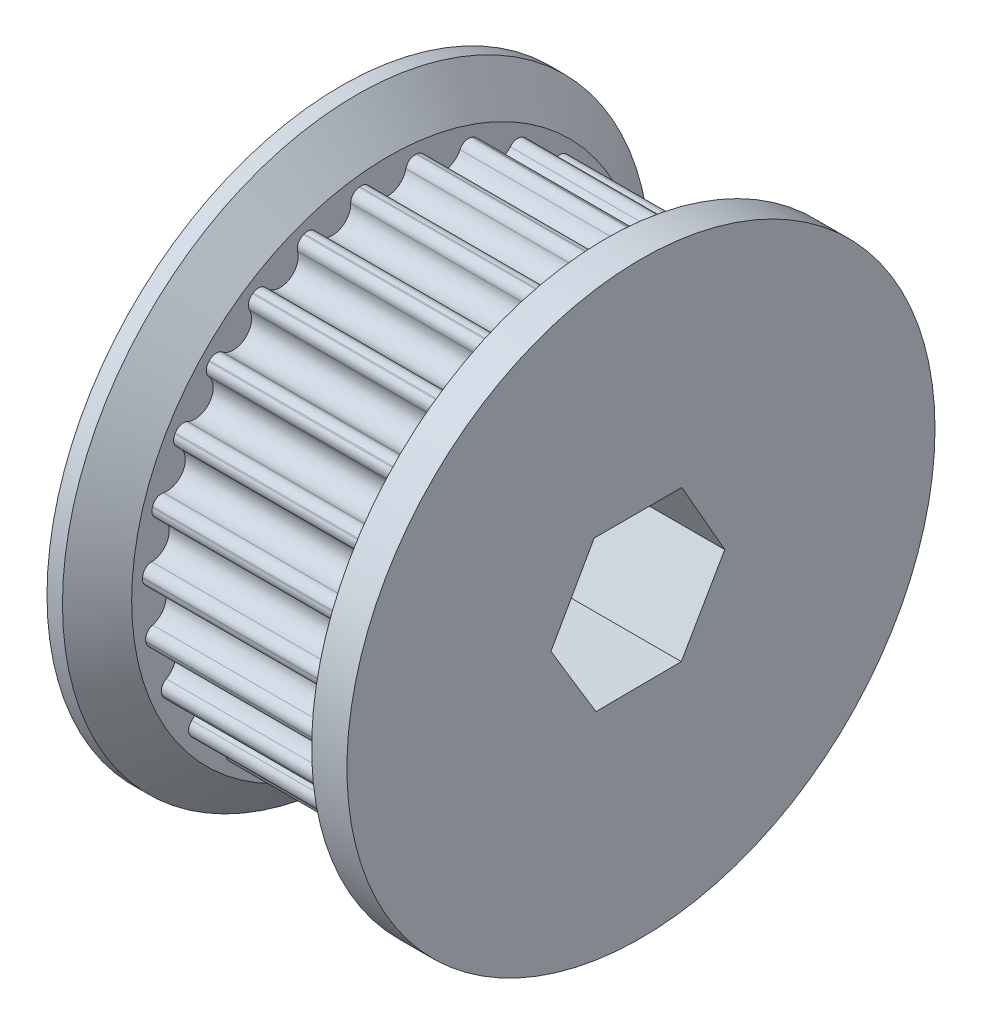
SolidWorks part; units mm, degrees
ref_plane "Front Plane" through (0, 0, 0) normal (0, 0, 1) x (1, 0, 0)
ref_plane "Top Plane" through (0, 0, 0) normal (0, 1, 0) x (1, 0, 0)
ref_plane "Right Plane" through (0, 0, 0) normal (1, 0, 0) x (0, 0, -1)
sketch "Sketch1" plane through (0, 0, 0) normal (1, 0, 0) x (0, 0, -1)
  circle A0 centre (0, 0) radius 20.915
  dimension "D1" = 41.83
extrude "Boss-Extrude1" add sketch "Sketch1" along normal blind 18.5 contours A0
sketch "Sketch8" plane through (18.5, 0, 0) normal (1, 0, 0) x (0, 0, -1)
  line L1 (0, 0) -> (0, 50.3807) construction
  line L7 (-2.5, 21.3391) -> (0, 0) construction
  line L8 (0, 0) -> (2.5, 21.3391) construction
  circle A0 centre (0, 0) radius 21.485 construction
  circle A2 centre (0, 0) radius 20.915 construction
  arc A3 (-1.4883, 20.862) -> (1.4883, 20.862) centre (0, 20.4573) ccw
  arc A6 (-1.4883, 20.862) -> (1.4883, 20.862) centre (0, 0) cw
  point P15 (0, 18.915)
  point P16 (0, 20.915)
  dimension "D4" = 1.5423
  dimension "D2" = 42.97
  dimension "D1" = 5
  dimension "D3" = 2.5
  dimension "D5" = 2
sketch "Sketch9" plane through (0, 0, 0) normal (-1, 0, 0) x (0, 0, 1)
  line L0 (-3.4711, 6.4445) -> (-7.1255, 0.0437)
  line L1 (-7.1255, 0.0437) -> (-3.4298, -6.3571)
  line L2 (-3.4298, -6.3571) -> (3.8268, -6.4097)
  line L3 (3.8268, -6.4097) -> (7.6559, -0.0635)
  line L4 (7.6559, -0.0635) -> (3.9818, 6.4445)
  line L5 (3.9818, 6.4445) -> (-3.4711, 6.4445)
extrude "Cut-Extrude6" cut sketch "Sketch8" against normal blind 43 contours A6 A3
fillet "Fillet4" radius 0.8 2 edges at (9.25, 20.862, -1.4883) (9.25, 20.862, 1.4883)
sketch "Sketch10" plane through (18.5, 0, 0) normal (1, 0, 0) x (0, 0, -1)
  circle A0 centre (0, 0) radius 25
  dimension "D1" = 50
sketch "Sketch11" plane through (0, 0, 0) normal (-1, 0, 0) x (0, 0, 1)
  circle A0 centre (0, 0) radius 25
  dimension "D1" = 50
pattern_circular "CirPattern1" count 27 over 360 about axis through (18.5, 0, 0) along (-1, 0, 0) of "Cut-Extrude6", "Fillet4"
extrude "Boss-Extrude7" add sketch "Sketch10" along normal blind 3
extrude "Boss-Extrude8" add sketch "Sketch11" along normal blind 4
chamfer "Chamfer1" distance 3.2 angle 40 1 edges at (0, 0, 25) first distance on face at (0, 0, 0)
extrude "Cut-Extrude5" cut sketch "Sketch9" against normal through all both and the other way through all
